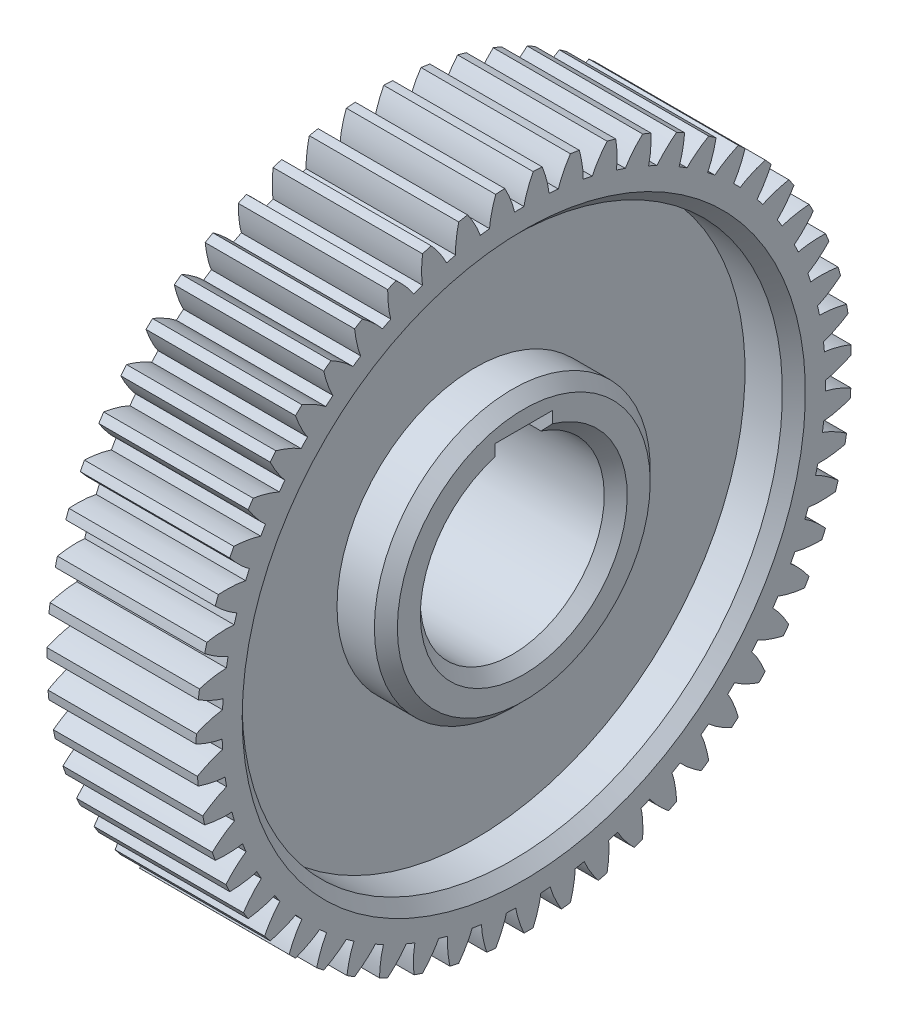
SolidWorks part; units mm, degrees
material "普通碳钢"
ref_plane "前视基准面" through (0, 0, 0) normal (0, 0, 1) x (1, 0, 0)
ref_plane "上视基准面" through (0, 0, 0) normal (0, 1, 0) x (1, 0, 0)
ref_plane "右视基准面" through (0, 0, 0) normal (1, 0, 0) x (0, 0, -1)
sketch "草图1" plane through (0, 0, 0) normal (1, 0, 0) x (0, 0, -1)
  line L0 (0, 0) -> (54.9939, 0.819) construction
  line L1 (0, 0) -> (54.8575, 3.9572) construction
  line L2 (0, 0) -> (54.9481, 2.389) construction
  arc A0 (56.9748, 1.6953) -> (56.9069, 3.2561) centre (0, 0) ccw
  circle A1 centre (0, 0) radius 51.6831 construction
  circle A2 centre (0, 0) radius 55 construction
  arc A3 (52.3102, 4.4596) -> (52.4999, 0.0973) centre (0, 0) ccw
  arc A4 (54.9939, 0.819) -> (54.8575, 3.9572) centre (0, 0) ccw construction
  spline S0 degree 4 poles (51.685, 0) (51.7341, 0.0013) (51.8323, 0.0061) (52.0281, 0.024) (52.3203, 0.0639) (52.659, 0.1242) (53.1204, 0.2247) (53.6538, 0.3644) (54.2565, 0.5497) (54.9253, 0.787) (55.8838, 1.1687) (57.1126, 1.7388) (58.4351, 2.4611) (59.8369, 3.3468) (61.322, 4.3933) (63.4591, 6.0772) (66.6417, 9.0782) (70.4631, 13.7479) (74.2547, 20.0497) (77.3635, 27.3378) (79.5466, 34.9502) (80.8558, 42.7578) (81.3656, 51.048) (80.9234, 61.3243) (78.8281, 73.429) (74.3653, 86.993) (68.0426, 99.3473) (61.4041, 109.1919) (53.9005, 118.3772) (46.9856, 125.4522) (39.4942, 131.9107) (31.5055, 137.728) (24.8466, 141.9894) (16.2249, 146.818) (8.1499, 150.5599) (0.7742, 153.4117) (-5.8006, 155.5514) (-9.5892, 156.6726) (-13.4062, 157.6924) (-17.249, 158.611) (-21.1143, 159.4288) (-24.9998, 160.146) (-28.9019, 160.763) (-32.3298, 161.2157) (-35.2738, 161.5417) (-37.7339, 161.7722) (-39.6995, 161.932) (-41.6762, 162.0673) (-43.6376, 162.1781) (-45.4532, 162.2567) (-47.0454, 162.3101) (-48.5409, 162.3442) (-49.7161, 162.3641) (-51.2708, 162.3747) (-52.3804, 162.3737) (-54.1953, 162.3589) (-55.5997, 162.3277) (-57.3037, 162.2809) (-58.8351, 162.2187) (-60.8621, 162.1217) (-62.8251, 161.9991) (-64.8286, 161.8509) (-66.8047, 161.6775) (-68.3961, 161.5236) (-70.3744, 161.3124) (-72.3555, 161.0761) (-74.3291, 160.815) (-75.908, 160.5862) (-76.6954, 160.467) (-77.0895, 160.4061) knots 0 0 0 0 0 0.000701 0.001401 0.002802 0.004203 0.005604 0.008133 0.010661 0.01319 0.015718 0.022839 0.02996 0.034653 0.039347 0.048734 0.068727 0.096889 0.125051 0.153212 0.181374 0.209535 0.237696 0.271429 0.327752 0.384075 0.440398 0.46856 0.496721 0.553044 0.581206 0.609367 0.637529 0.66569 0.722013 0.736094 0.750174 0.764255 0.778336 0.792417 0.806497 0.820578 0.834659 0.84874 0.85578 0.86282 0.869861 0.876901 0.883942 0.890982 0.895509 0.900036 0.904564 0.909091 0.914773 0.920455 0.926136 0.931818 0.9375 0.943182 0.954545 0.960227 0.965909 0.971591 0.977273 0.988636 0.994318 1 1 1 1 1 construction
  spline S1 degree 4 poles (52.4999, 0.0973) (52.5879, 0.1132) (52.7722, 0.1489) (53.1289, 0.227) (53.6538, 0.3644) (54.2565, 0.5497) (54.9253, 0.787) (55.6934, 1.0929) (56.2862, 1.3584) (56.7115, 1.5632) (56.9748, 1.6953) knots 0.002928 0.002928 0.002928 0.002928 0.002928 0.004203 0.005604 0.008133 0.010661 0.01319 0.015718 0.019918 0.019918 0.019918 0.019918 0.019918
  spline S2 degree 4 poles (52.3102, 4.4596) (52.3993, 4.4515) (52.586, 4.4319) (52.9481, 4.3851) (53.483, 4.2938) (54.0995, 4.1614) (54.7863, 3.9831) (55.5781, 3.745) (56.1917, 3.5319) (56.6331, 3.3649) (56.9069, 3.2561) knots 0.002928 0.002928 0.002928 0.002928 0.002928 0.004203 0.005604 0.008133 0.010661 0.01319 0.015718 0.019918 0.019918 0.019918 0.019918 0.019918
  dimension "D1" = 114
  dimension "D2" = 103.3662
  dimension "D3" = 110
  dimension "D4" = 105
  dimension "D5" = 3.1416
extrude "凸台-拉伸1" add sketch "草图1" along normal blind 13 and the other way blind 13
ref_axis "基准轴1" through (13, 0, 0) along (-1, 0, 0)
pattern_circular "阵列(圆周)1" count 55 over 360 about axis through (13, 0, 0) along (-1, 0, 0) of "凸台-拉伸1"
sketch "草图2" plane through (-13, 0, 0) normal (-1, 0, 0) x (0, 0, 1)
  circle A0 centre (0, 0) radius 47
  circle A1 centre (0, 0) radius 24
  dimension "D1" = 94
  dimension "D2" = 48
extrude "切除-拉伸1" cut sketch "草图2" against normal blind 8.5
mirror "镜向1" about plane through (0, 0, 0) normal (1, 0, 0) of "切除-拉伸1"
sketch "草图3" plane through (-13, 0, 0) normal (-1, 0, 0) x (0, 0, 1)
  line L0 (0, 33.8088) -> (0, 0) construction
  line L4 (0, 0) -> (0, -16) construction
  circle A0 centre (0, 0) radius 16
  dimension "D3" = 32
extrude "切除-拉伸2" cut sketch "草图3" against normal through all
chamfer "倒角1" distance 2 angle 45 6 edges at (-13, 0, 16) (-13, 0, 24) (-13, 0, 47) (13, 0, 16) (13, 0, 24) (13, 0, 47)
sketch "草图4" plane through (-13, 0, 0) normal (-1, 0, 0) x (0, 0, 1)
  line L0 (0, 36.3553) -> (0, -16) construction
  line L2 (-5, 19.3) -> (5, 19.3)
  line L3 (-5, 19.3) -> (-5, 0)
  line L4 (-5, 0) -> (5, 0)
  line L5 (5, 19.3) -> (5, 0)
  line L6 (-5, 19.3) -> (5, 0) construction
  line L7 (-5, 0) -> (5, 19.3) construction
  circle A0 centre (0, 0) radius 16 construction
  point P5 (0, 9.65)
  dimension "D1" = 10
  dimension "D2" = 35.3
extrude "切除-拉伸3" cut sketch "草图4" against normal through all
equation "\"m\"= 2"
equation "\"z\"= 55"
equation "\"a\"= 20"
equation "\"d\"= \"m\" * \"z\"'分度圆直径"
equation "\"Db\"= \"d\" * cos ( \"a\" )'基圆直径"
equation "\"Ha\"= \"m\"'齿顶高"
equation "\"Hf\"= 1.25 * \"m\"'齿根高"
equation "\"Da\"= \"d\" + \"Ha\" * 2'齿顶圆直径"
equation "\"Df\"= \"d\" - \"Hf\" * 2'齿根圆直径"
equation "\"p\"= \"m\" * pi'齿距"
equation "\"D4@草图1\"=\"Df\""
equation "\"D2@草图1\"=\"Db\""
equation "\"D3@草图1\"=\"d\""
equation "\"D1@草图1\"=\"Da\""
equation "\"D5@草图1\"=\"p\"/2"
